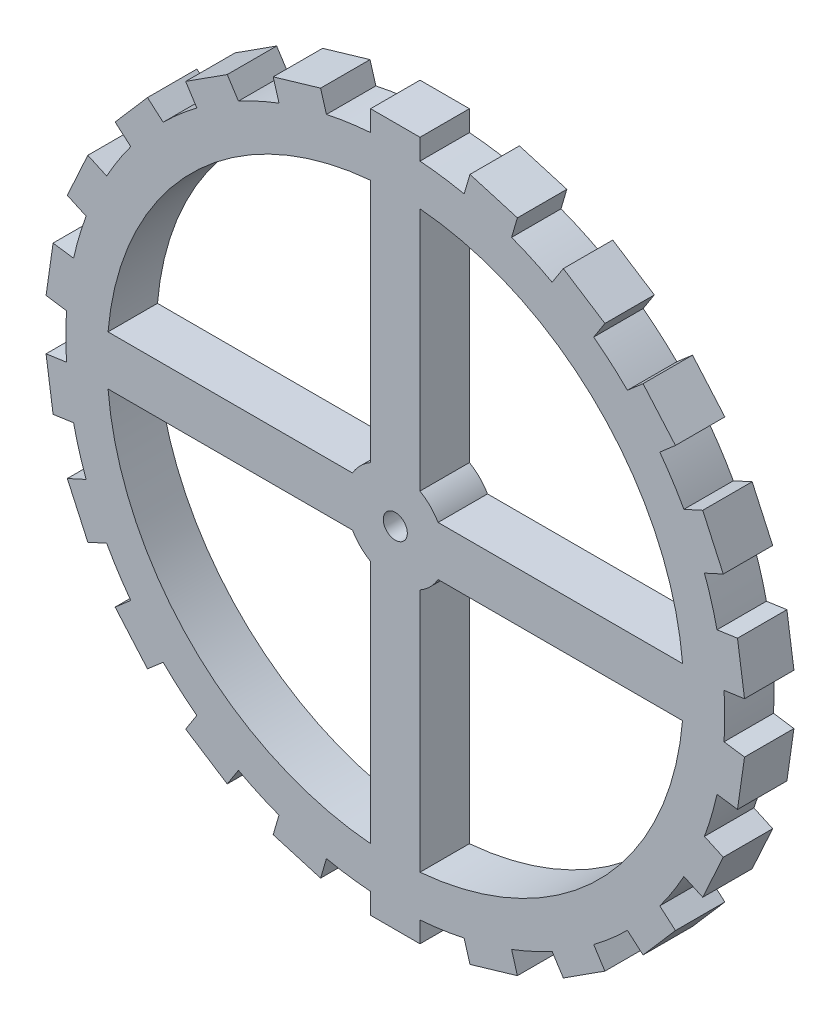
SolidWorks part; units mm, degrees
ref_plane "Front Plane" through (0, 0, 0) normal (0, 0, 1) x (1, 0, 0)
ref_plane "Top Plane" through (0, 0, 0) normal (0, 1, 0) x (1, 0, 0)
ref_plane "Right Plane" through (0, 0, 0) normal (1, 0, 0) x (0, 0, -1)
sketch "Sketch1" plane through (0, 0, 0) normal (0, 0, 1) x (1, 0, 0)
  line L0 (-1.905, 3.2996) -> (-1.905, 22.1432)
  line L2 (1.905, -22.1432) -> (1.905, -3.2996)
  line L4 (-1.905, -22.1432) -> (-1.905, -3.2996)
  line L5 (1.905, -22.1432) -> (-1.905, 22.1432) construction
  line L6 (1.905, 22.1432) -> (-1.905, -22.1432) construction
  line L7 (-22.1432, -1.905) -> (-3.2996, -1.905)
  line L9 (-22.1432, 1.905) -> (-3.2996, 1.905)
  line L11 (-22.1432, -1.905) -> (22.1432, 1.905) construction
  line L12 (-22.1432, 1.905) -> (22.1432, -1.905) construction
  line L13 (3.2996, 1.905) -> (22.1432, 1.905)
  line L14 (3.2996, -1.905) -> (22.1432, -1.905)
  line L15 (1.905, 3.2996) -> (1.905, 22.1432)
  circle A0 centre (0, 0) radius 25.4
  arc A1 (-22.1432, -1.905) -> (-1.905, -22.1432) centre (0, 0) ccw
  circle A2 centre (0, 0) radius 0.9271
  arc A4 (-3.2996, -1.905) -> (-1.905, -3.2996) centre (0, 0) ccw
  arc A5 (-1.905, 3.2996) -> (-3.2996, 1.905) centre (0, 0) ccw
  arc A6 (3.2996, 1.905) -> (1.905, 3.2996) centre (0, 0) ccw
  arc A7 (1.905, -3.2996) -> (3.2996, -1.905) centre (0, 0) ccw
  arc A8 (1.905, -22.1432) -> (22.1432, -1.905) centre (0, 0) ccw
  arc A9 (22.1432, 1.905) -> (1.905, 22.1432) centre (0, 0) ccw
  arc A10 (-1.905, 22.1432) -> (-22.1432, 1.905) centre (0, 0) ccw
  dimension "D1" = 50.8
  dimension "D2" = 44.45
  dimension "D3" = 1.8542
  dimension "D5" = 3.81
  dimension "D6" = 3.81
extrude "Boss-Extrude1" add sketch "Sketch1" along normal blind 3.81
sketch "Sketch2" plane through (0, 0, 3.81) normal (0, 0, 1) x (1, 0, 0)
  line L0 (5.308, 24.8392) -> (5.7575, 26.3701)
  line L2 (-1.905, 25.3285) -> (-1.905, 26.924)
  line L3 (-1.905, 26.924) -> (1.905, 26.924)
  line L4 (1.905, 25.3285) -> (1.905, 26.924)
  line L5 (0, 25.4) -> (1.905, 26.924) construction
  line L6 (-1.905, 26.924) -> (1.905, 23.876) construction
  line L7 (5.7575, 26.3701) -> (9.4132, 25.2967)
  line L8 (8.9637, 23.7658) -> (9.4132, 25.2967)
  line L9 (7.156, 24.3711) -> (9.4132, 25.2967) construction
  line L10 (5.7575, 26.3701) -> (8.5545, 22.3722) construction
  line L11 (12.091, 22.3376) -> (12.9536, 23.6798)
  line L12 (12.9536, 23.6798) -> (16.1588, 21.62)
  line L13 (15.2962, 20.2777) -> (16.1588, 21.62)
  line L14 (13.7323, 21.3678) -> (16.1588, 21.62) construction
  line L15 (12.9536, 23.6798) -> (14.5109, 19.0558) construction
  line L16 (17.8945, 18.0263) -> (19.1003, 19.0712)
  line L17 (19.1003, 19.0712) -> (21.5953, 16.1918)
  line L18 (20.3895, 15.1469) -> (21.5953, 16.1918)
  line L19 (19.196, 16.6335) -> (21.5953, 16.1918) construction
  line L20 (19.1003, 19.0712) -> (19.2918, 14.1958) construction
  line L21 (22.2482, 12.2547) -> (23.6996, 12.9175)
  line L22 (23.6996, 12.9175) -> (25.2823, 9.4518)
  line L23 (23.8309, 8.789) -> (25.2823, 9.4518)
  line L24 (23.1047, 10.5515) -> (25.2823, 9.4518) construction
  line L25 (23.6996, 12.9175) -> (22.5097, 8.1856) construction
  line L26 (24.7995, 5.4902) -> (26.3788, 5.7173)
  line L27 (26.3788, 5.7173) -> (26.9211, 1.9461)
  line L28 (25.3418, 1.719) -> (26.9211, 1.9461)
  line L29 (25.1415, 3.6148) -> (26.9211, 1.9461) construction
  line L30 (26.3788, 5.7173) -> (23.9041, 1.5123) construction
  line L31 (25.3418, -1.719) -> (26.9211, -1.9461)
  line L32 (26.9211, -1.9461) -> (26.3788, -5.7173)
  line L33 (24.7995, -5.4902) -> (26.3788, -5.7173)
  line L34 (25.1415, -3.6148) -> (26.3788, -5.7173) construction
  line L35 (26.9211, -1.9461) -> (23.3619, -5.2835) construction
  line L36 (23.8309, -8.789) -> (25.2823, -9.4518)
  line L37 (25.2823, -9.4518) -> (23.6996, -12.9175)
  line L38 (22.2482, -12.2547) -> (23.6996, -12.9175)
  line L39 (23.1047, -10.5515) -> (23.6996, -12.9175) construction
  line L40 (25.2823, -9.4518) -> (20.927, -11.6513) construction
  line L41 (20.3895, -15.1469) -> (21.5953, -16.1918)
  line L42 (21.5953, -16.1918) -> (19.1003, -19.0712)
  line L43 (17.8945, -18.0263) -> (19.1003, -19.0712)
  line L44 (19.196, -16.6335) -> (19.1003, -19.0712) construction
  line L45 (21.5953, -16.1918) -> (16.7968, -17.0752) construction
  line L46 (15.2962, -20.2777) -> (16.1588, -21.62)
  line L47 (16.1588, -21.62) -> (12.9536, -23.6798)
  line L48 (12.091, -22.3376) -> (12.9536, -23.6798)
  line L49 (13.7323, -21.3678) -> (12.9536, -23.6798) construction
  line L50 (16.1588, -21.62) -> (11.3058, -21.1157) construction
  line L51 (8.9637, -23.7658) -> (9.4132, -25.2967)
  line L52 (9.4132, -25.2967) -> (5.7575, -26.3701)
  line L53 (5.308, -24.8392) -> (5.7575, -26.3701)
  line L54 (7.156, -24.3711) -> (5.7575, -26.3701) construction
  line L55 (9.4132, -25.2967) -> (4.8988, -23.4456) construction
  line L56 (1.905, -25.3285) -> (1.905, -26.924)
  line L57 (1.905, -26.924) -> (-1.905, -26.924)
  line L58 (-1.905, -25.3285) -> (-1.905, -26.924)
  line L59 (0, -25.4) -> (-1.905, -26.924) construction
  line L60 (1.905, -26.924) -> (-1.905, -23.876) construction
  line L61 (-5.308, -24.8392) -> (-5.7575, -26.3701)
  line L62 (-5.7575, -26.3701) -> (-9.4132, -25.2967)
  line L63 (-8.9637, -23.7658) -> (-9.4132, -25.2967)
  line L64 (-7.156, -24.3711) -> (-9.4132, -25.2967) construction
  line L65 (-5.7575, -26.3701) -> (-8.5545, -22.3722) construction
  line L66 (-12.091, -22.3376) -> (-12.9536, -23.6798)
  line L67 (-12.9536, -23.6798) -> (-16.1588, -21.62)
  line L68 (-15.2962, -20.2777) -> (-16.1588, -21.62)
  line L69 (-13.7323, -21.3678) -> (-16.1588, -21.62) construction
  line L70 (-12.9536, -23.6798) -> (-14.5109, -19.0558) construction
  line L71 (-17.8945, -18.0263) -> (-19.1003, -19.0712)
  line L72 (-19.1003, -19.0712) -> (-21.5953, -16.1918)
  line L73 (-20.3895, -15.1469) -> (-21.5953, -16.1918)
  line L74 (-19.196, -16.6335) -> (-21.5953, -16.1918) construction
  line L75 (-19.1003, -19.0712) -> (-19.2918, -14.1958) construction
  line L76 (-22.2482, -12.2547) -> (-23.6996, -12.9175)
  line L77 (-23.6996, -12.9175) -> (-25.2823, -9.4518)
  line L78 (-23.8309, -8.789) -> (-25.2823, -9.4518)
  line L79 (-23.1047, -10.5515) -> (-25.2823, -9.4518) construction
  line L80 (-23.6996, -12.9175) -> (-22.5097, -8.1856) construction
  line L81 (-24.7995, -5.4902) -> (-26.3788, -5.7173)
  line L82 (-26.3788, -5.7173) -> (-26.9211, -1.9461)
  line L83 (-25.3418, -1.719) -> (-26.9211, -1.9461)
  line L84 (-25.1415, -3.6148) -> (-26.9211, -1.9461) construction
  line L85 (-26.3788, -5.7173) -> (-23.9041, -1.5123) construction
  line L86 (-25.3418, 1.719) -> (-26.9211, 1.9461)
  line L87 (-26.9211, 1.9461) -> (-26.3788, 5.7173)
  line L88 (-24.7995, 5.4902) -> (-26.3788, 5.7173)
  line L89 (-25.1415, 3.6148) -> (-26.3788, 5.7173) construction
  line L90 (-26.9211, 1.9461) -> (-23.3619, 5.2835) construction
  line L91 (-23.8309, 8.789) -> (-25.2823, 9.4518)
  line L92 (-25.2823, 9.4518) -> (-23.6996, 12.9175)
  line L93 (-22.2482, 12.2547) -> (-23.6996, 12.9175)
  line L94 (-23.1047, 10.5515) -> (-23.6996, 12.9175) construction
  line L95 (-25.2823, 9.4518) -> (-20.927, 11.6513) construction
  line L96 (-20.3895, 15.1469) -> (-21.5953, 16.1918)
  line L97 (-21.5953, 16.1918) -> (-19.1003, 19.0712)
  line L98 (-17.8945, 18.0263) -> (-19.1003, 19.0712)
  line L99 (-19.196, 16.6335) -> (-19.1003, 19.0712) construction
  line L100 (-21.5953, 16.1918) -> (-16.7968, 17.0752) construction
  line L101 (-15.2962, 20.2777) -> (-16.1588, 21.62)
  line L102 (-16.1588, 21.62) -> (-12.9536, 23.6798)
  line L103 (-12.091, 22.3376) -> (-12.9536, 23.6798)
  line L104 (-13.7323, 21.3678) -> (-12.9536, 23.6798) construction
  line L105 (-16.1588, 21.62) -> (-11.3058, 21.1157) construction
  line L106 (-8.9637, 23.7658) -> (-9.4132, 25.2967)
  line L107 (-9.4132, 25.2967) -> (-5.7575, 26.3701)
  line L108 (-5.308, 24.8392) -> (-5.7575, 26.3701)
  line L109 (-7.156, 24.3711) -> (-5.7575, 26.3701) construction
  line L110 (-9.4132, 25.2967) -> (-4.8988, 23.4456) construction
  circle A0 centre (0, 0) radius 25.4 construction
  arc A1 (1.905, 25.3285) -> (-1.905, 25.3285) centre (0, 0) ccw
  arc A2 (8.9637, 23.7658) -> (5.308, 24.8392) centre (0, 0) ccw
  arc A3 (15.2962, 20.2777) -> (12.091, 22.3376) centre (0, 0) ccw
  arc A4 (20.3895, 15.1469) -> (17.8945, 18.0263) centre (0, 0) ccw
  arc A5 (23.8309, 8.789) -> (22.2482, 12.2547) centre (0, 0) ccw
  arc A6 (25.3418, 1.719) -> (24.7995, 5.4902) centre (0, 0) ccw
  arc A7 (24.7995, -5.4902) -> (25.3418, -1.719) centre (0, 0) ccw
  arc A8 (22.2482, -12.2547) -> (23.8309, -8.789) centre (0, 0) ccw
  arc A9 (17.8945, -18.0263) -> (20.3895, -15.1469) centre (0, 0) ccw
  arc A10 (12.091, -22.3376) -> (15.2962, -20.2777) centre (0, 0) ccw
  arc A11 (5.308, -24.8392) -> (8.9637, -23.7658) centre (0, 0) ccw
  arc A12 (-1.905, -25.3285) -> (1.905, -25.3285) centre (0, 0) ccw
  arc A13 (-8.9637, -23.7658) -> (-5.308, -24.8392) centre (0, 0) ccw
  arc A14 (-15.2962, -20.2777) -> (-12.091, -22.3376) centre (0, 0) ccw
  arc A15 (-20.3895, -15.1469) -> (-17.8945, -18.0263) centre (0, 0) ccw
  arc A16 (-23.8309, -8.789) -> (-22.2482, -12.2547) centre (0, 0) ccw
  arc A17 (-25.3418, -1.719) -> (-24.7995, -5.4902) centre (0, 0) ccw
  arc A18 (-24.7995, 5.4902) -> (-25.3418, 1.719) centre (0, 0) ccw
  arc A19 (-22.2482, 12.2547) -> (-23.8309, 8.789) centre (0, 0) ccw
  arc A20 (-17.8945, 18.0263) -> (-20.3895, 15.1469) centre (0, 0) ccw
  arc A21 (-12.091, 22.3376) -> (-15.2962, 20.2777) centre (0, 0) ccw
  arc A22 (-5.308, 24.8392) -> (-8.9637, 23.7658) centre (0, 0) ccw
  point P0 (0, 25.4)
  point P14 (7.156, 24.3711)
  point P21 (13.7323, 21.3678)
  point P28 (19.196, 16.6335)
  point P35 (23.1047, 10.5515)
  point P42 (25.1415, 3.6148)
  point P49 (25.1415, -3.6148)
  point P56 (23.1047, -10.5515)
  point P63 (19.196, -16.6335)
  point P70 (13.7323, -21.3678)
  point P77 (7.156, -24.3711)
  point P84 (0, -25.4)
  point P91 (-7.156, -24.3711)
  point P98 (-13.7323, -21.3678)
  point P105 (-19.196, -16.6335)
  point P112 (-23.1047, -10.5515)
  point P119 (-25.1415, -3.6148)
  point P126 (-25.1415, 3.6148)
  point P133 (-23.1047, 10.5515)
  point P140 (-19.196, 16.6335)
  point P147 (-13.7323, 21.3678)
  point P154 (-7.156, 24.3711)
  dimension "D1" = 3.048
  dimension "D2" = 3.81
  dimension "D3" = 22
extrude "Boss-Extrude2" add sketch "Sketch2" against normal up to surface (3.81 mm away) up to face at (8.259, -8.259, 0)
